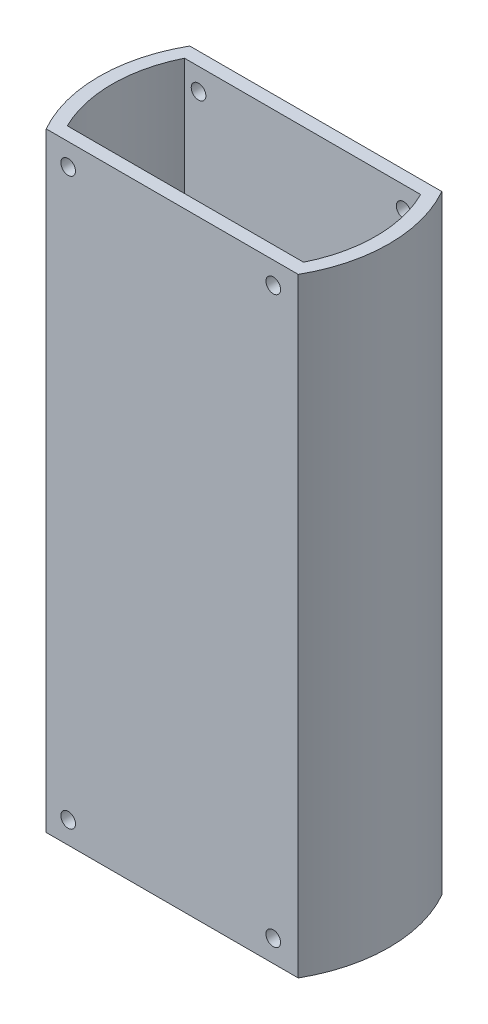
SolidWorks part; units mm, degrees
ref_plane "Front Plane" through (0, 0, 0) normal (0, 0, 1) x (1, 0, 0)
ref_plane "Top Plane" through (0, 0, 0) normal (0, 1, 0) x (1, 0, 0)
ref_plane "Right Plane" through (0, 0, 0) normal (1, 0, 0) x (0, 0, -1)
sketch "Sketch2" plane through (0, 0, 0) normal (0, 1, 0) x (1, 0, 0)
  line L0 (0, -20) -> (0, 20)
  line L1 (-45.2797, 20) -> (45.2797, 20)
  line L2 (-45.2797, -20) -> (45.2797, -20)
  line L3 (-43.0116, -24.5) -> (43.0116, -24.5)
  line L4 (-43.0116, 24.5) -> (43.0116, 24.5)
  circle A0 centre (0, 0) radius 49.5
  circle A1 centre (0, 0) radius 45
  point P7 (0, 0)
  point P9 (0, 20)
  point P13 (0, -20)
  point P16 (0, -24.5)
  point P19 (0, 24.5)
  dimension "D1" = 99
  dimension "D2" = 90
  dimension "D3" = 40
  dimension "D4" = 4.5
  dimension "D5" = 4.5
extrude "Boss-Extrude1" add sketch "Sketch2" along normal blind 208 contours A1 L1 A0 L2 | A1 L2 A0 L3 | L3 A1 L2 | A1 L3 A0 L2 | A1 L1 A0 L4 | A1 L2 A0 L1 | L1 A1 L4 | A1 L4 A0 L1 region at (0, 0, 22.2254) region at (0, 0, -22.2254) region at (-41.628, 0, 22.2718) region at (-45.7559, 0, 0) region at (45.7559, 0, 0) region at (41.628, 0, 22.2718) region at (-41.628, 0, -22.2718) region at (41.628, 0, -22.2718)
sketch "Sketch3" plane through (0, 0, 24.5) normal (0, 0, 1) x (1, 0, 0)
  line L0 (0, 208) -> (0, 0) construction
  line L1 (-43.0116, 208) -> (-35.5116, 208)
  line L2 (-43.0116, 208) -> (-43.0116, 200.5)
  line L3 (-43.0116, 200.5) -> (-35.5116, 200.5)
  line L4 (-35.5116, 208) -> (-35.5116, 200.5)
  line L5 (-43.0116, 208) -> (43.0116, 208) construction
  line L6 (-43.0116, 104) -> (43.0116, 104) construction
  line L7 (-43.0116, 208) -> (-43.0116, 0) construction
  line L8 (43.0116, 208) -> (43.0116, 0) construction
  line L9 (37.4884, 198.7679) -> (37.4884, 202.2321)
  line L10 (-32.5116, 198.7679) -> (-32.5116, 202.2321)
  line L11 (-32.5116, 202.2321) -> (-35.5116, 203.9641)
  line L12 (-35.5116, 203.9641) -> (-38.5116, 202.2321)
  line L13 (-38.5116, 202.2321) -> (-38.5116, 198.7679)
  line L14 (-38.5116, 198.7679) -> (-35.5116, 197.0359)
  line L15 (-35.5116, 197.0359) -> (-32.5116, 198.7679)
  line L16 (37.4884, 202.2321) -> (34.4884, 203.9641)
  line L17 (34.4884, 203.9641) -> (31.4884, 202.2321)
  line L18 (31.4884, 202.2321) -> (31.4884, 198.7679)
  line L19 (31.4884, 198.7679) -> (34.4884, 197.0359)
  line L20 (34.4884, 197.0359) -> (37.4884, 198.7679)
  line L21 (37.4884, 5.7679) -> (37.4884, 9.2321)
  line L22 (37.4884, 9.2321) -> (34.4884, 10.9641)
  line L23 (34.4884, 10.9641) -> (31.4884, 9.2321)
  line L24 (31.4884, 9.2321) -> (31.4884, 5.7679)
  line L25 (31.4884, 5.7679) -> (34.4884, 4.0359)
  line L26 (34.4884, 4.0359) -> (37.4884, 5.7679)
  line L27 (-32.5116, 5.7679) -> (-32.5116, 9.2321)
  line L28 (-32.5116, 9.2321) -> (-35.5116, 10.9641)
  line L29 (-35.5116, 10.9641) -> (-38.5116, 9.2321)
  line L30 (-38.5116, 9.2321) -> (-38.5116, 5.7679)
  line L31 (-38.5116, 5.7679) -> (-35.5116, 4.0359)
  line L32 (-35.5116, 4.0359) -> (-32.5116, 5.7679)
  line L33 (-43.0116, 0) -> (43.0116, 0) construction
  circle A0 centre (-35.5116, 200.5) radius 2.5
  circle A1 centre (34.4884, 200.5) radius 2.5
  circle A2 centre (34.4884, 7.5) radius 2.5
  circle A3 centre (-35.5116, 7.5) radius 2.5
  circle A4 centre (-35.5116, 200.5) radius 3 construction
  point P32 (-32.5116, 7.5)
  dimension "D3" = 5
  dimension "D1" = 7.5
  dimension "D2" = 7.5
  dimension "D8" = 4.5
  dimension "D9" = 7.5
  dimension "D10" = 7.5
  dimension "D6" = 2
  dimension "D4" = 2
  dimension "D5" = 2
  dimension "D7" = 2
extrude "Cut-Extrude1" cut sketch "Sketch3" against normal blind 60 contours A0 | A1 | A3 | A2
